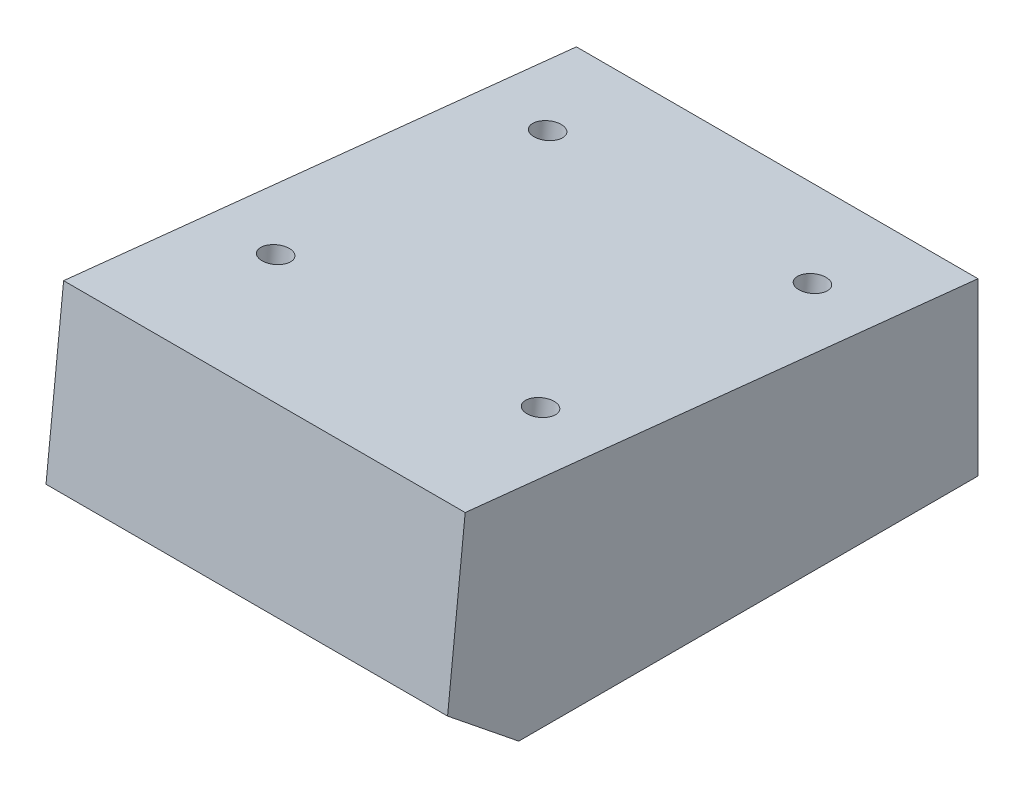
SolidWorks part; units mm, degrees
note: '?' marks a value the reader was unsure of.
ref_plane "Plan de face" through (0, 0, 0) normal (0, 0, 1) x (1, 0, 0)
ref_plane "Plan de dessus" through (0, 0, 0) normal (0, 1, 0) x (1, 0, 0)
ref_plane "Plan de droite" through (0, 0, 0) normal (1, 0, 0) x (0, 0, -1)
sketch "Esquisse1" plane through (0, 0, 0) normal (1, 0, 0) x (0, 0, -1)
  line L3 (53.75, 20) -> (-6.2679, 26.3081)
  line L4 (-8.3285, 6.7027) -> (-6.2679, 26.3081)
  line L5 (0, 0) -> (-8.3285, 6.7027)
  line L8 (53.75, 0) -> (53.75, 20)
  line L9 (0, 0) -> (53.75, 0)
  dimension "D1" = 6
  dimension "D2" = 53.75
  dimension "D3" = 20
  dimension "D4" = 6.7027
  dimension "D5" = 237.173
extrude "Boss.-Extru.1" add sketch "Esquisse1" against normal offset from surface 1 and the other way offset from surface (23.5 mm away) 1
sketch "Esquisse2" plane through (0, 0, 0) normal (0, -1, 0) x (1, 0, 0)
  line L0 (-22.5, 0) -> (-22.5, -54) construction
  line L1 (-22.6, 0) -> (22.6, 0)
  line L2 (-22.6, 0) -> (-22.6, -53.75)
  line L3 (-22.6, -53.75) -> (22.6, -53.75)
  line L4 (22.6, 0) -> (22.6, -53.75)
  line L5 (-23.5, 0) -> (23.5, 0) construction
  line L6 (-23.5, -53.75) -> (23.5, -53.75) construction
  point P6 (0, -53.75)
  dimension "D1" = 0.1
extrude "Enlèv. mat.-Extru.1" cut sketch "Esquisse2" against normal blind 4.05
sketch "Esquisse3" plane through (0, 25.3691, -2.6664) normal (0, 0.9945, -0.1045) x (1, 0, 0)
  circle A0 centre (-15.5, 39.929) radius 1.6
  circle A1 centre (15.5, 39.929) radius 1.6
  circle A2 centre (15.5, 7.929) radius 1.6
  circle A3 centre (-15.5, 7.929) radius 1.6
extrude "Enlèv. mat.-Extru.2" cut sketch "Esquisse3" against normal up to next
ref_axis "Axe1" through (15.5, -0.6504, -40.0806) along (0, 0.9945, -0.1045)?
ref_axis "Axe2" through (15.5, -1.978, -7.7648) along (0, 0.9945, -0.1045)?
ref_axis "Axe5" through (-15.5, -2.4898, -7.711) along (0, 0.9945, -0.1045)?
ref_axis "Axe6" through (-15.5, -2.3877, -39.898) along (0, 0.9945, -0.1045)?
hole_wizard "Trou pour taraudage pour trou taraudé M31" positions "Esquisse6" profile "Esquisse5" hole size "M3" standard "ISO"
sketch "Esquisse6" plane through (0, 0, 0) normal (0, -0.779, 0.627) x (-1, 0, 0)
  point P0 (13.5, -5.5483)
  point P3 (-13.5, -5.5483)
sketch "Esquisse5" plane through (-13.5, 3.4786, 4.3223) normal (1, 0, 0) x (0, -0.627, -0.779)
  line L0 (0, 0) -> (0, 5.7511)
  line L1 (0, 5.7511) -> (1.25, 5)
  line L2 (1.25, 5) -> (1.25, 0)
  line L5 (1.25, 0) -> (0, 0)
  line L10 (0, 5.7511) -> (-1.25, 5) construction
  line L11 (0, -6.35) -> (0, 107.95) construction
  dimension "Diamètre du perçage" = 2.5
  dimension "Profondeur du perçage" = 5
  dimension "Angle de pointe" = 118
